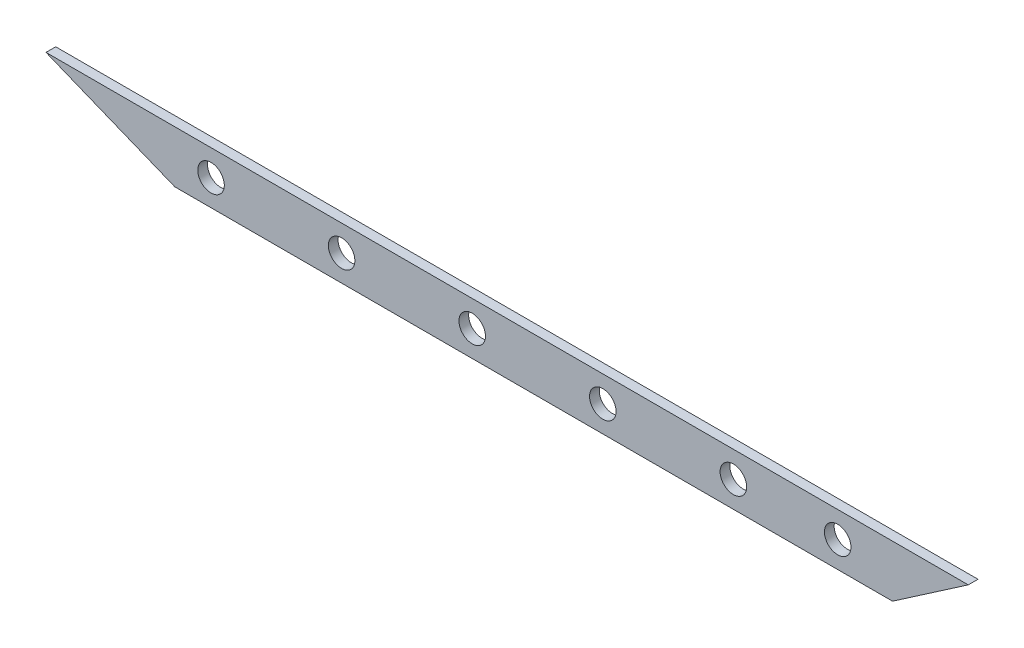
SolidWorks part; units mm, degrees
material "5052-H32"
ref_plane "Front Plane" through (0, 0, 0) normal (0, 0, 1) x (1, 0, 0)
ref_plane "Top Plane" through (0, 0, 0) normal (0, 1, 0) x (1, 0, 0)
ref_plane "Right Plane" through (0, 0, 0) normal (1, 0, 0) x (0, 0, -1)
sketch "Sketch1" plane through (0, 0, 0) normal (0, 0, 1) x (1, 0, 0)
  line L1 (428.1206, 33.3333) -> (428.1206, 28.5708)
  line L3 (428.1206, 28.5708) -> (0, 28.5708)
  line L4 (0, 28.5708) -> (-98.8794, 3.851)
  line L6 (-98.8794, 3.851) -> (-31.8794, -96.649)
  line L7 (428.1206, 28.5708) -> (403.1206, -71.149)
  line L9 (403.1206, -71.149) -> (366, -96.649)
  line L10 (-31.8794, -96.649) -> (366, -96.649)
  circle A0 centre (32, -83.899) radius 6.5
  circle A1 centre (96, -83.899) radius 6.5
  circle A2 centre (160, -83.899) radius 6.5
  circle A3 centre (224, -83.899) radius 6.5
  circle A4 centre (288, -83.899) radius 6.5
  circle A5 centre (339.1206, -83.899) radius 6.5
  point P0 (-48.8794, -71.149)
  point P2 (-31.8794, -96.649)
  point P8 (48, -83.899)
  point P9 (403.1206, -71.149)
  dimension "D2" = 16
  dimension "D4" = 64
  dimension "D1" = 25.5
  dimension "D3" = 75
  dimension "D5" = 25
  dimension "D6" = 64
  dimension "D7" = 527
  dimension "D9" = 64
  dimension "D10" = 64
  dimension "D11" = 64
  dimension "D12" = 123.69
  dimension "D13" = 12.75
extrude "Boss-Extrude1" add sketch "Sketch1" along normal blind 4.7625 contours L3 L4 L6 L10 L9 L7
extrude "Cut-Extrude1" cut sketch "Sketch1<4>" along normal through all contours A0 | A1 | A2 | A3 | A4 | A5 region at (32, -83.899, 0)
sketch "Sketch1<4>" plane through (0, 0, 0) normal (0, 0, 1) x (1, 0, 0) same geometry as "Sketch1"
sketch "Sketch2" plane through (0, 0, 0) normal (0, 0, -1) x (-1, 0, 0)
  circle A0 centre (-307.1206, -83.899) radius 6.5
  circle A2 centre (-249.5603, -111.8778) radius 6.5
  circle A3 centre (-192, -83.899) radius 6.5
  circle A4 centre (-128, -83.899) radius 6.5
  circle A5 centre (-64, -83.899) radius 6.5
  circle A6 centre (0, -83.899) radius 6.5
  dimension "D2" = 0
  dimension "D3" = 64
  dimension "D4" = 64
  dimension "D5" = 64
  dimension "D6" = 64
  dimension "D7" = 64
  dimension "D1" = 32
sketch "Sketch5" plane through (0, 0, 0) normal (0, 0, -1) x (-1, 0, 0)
  line L0 (48.8794, -71.149) -> (-14.2353, -96.649)
  line L1 (31.8794, -96.649) -> (-366, -96.649) construction
  line L2 (-14.2353, -96.649) -> (31.8794, -96.649)
  line L3 (31.8794, -96.649) -> (48.8794, -71.149)
  line L6 (-366, -96.649) -> (-403.1206, -71.149)
  line L7 (-403.1206, -71.149) -> (-352, -71.149)
  line L9 (-352, -71.149) -> (-326.5, -96.649)
  line L11 (-366, -96.649) -> (-326.5, -96.649)
  dimension "D1" = 22
  dimension "D2" = 45
extrude "Cut-Extrude2" [suppressed] cut sketch "Sketch5" against normal up to next
sketch "Sketch6" plane through (0, 0, 4.7625) normal (0, 0, 1) x (1, 0, 0)
  line L0 (-48.8794, -71.149) -> (14.2353, -96.649)
  line L1 (-31.8794, -96.649) -> (366, -96.649) construction
  line L2 (14.2353, -96.649) -> (-31.8794, -96.649)
  line L3 (-31.8794, -96.649) -> (-48.8794, -71.149)
  dimension "D1" = 158
extrude "Cut-Extrude3" cut sketch "Sketch6" against normal blind 10
sketch "Sketch7" plane through (0, 0, 4.7625) normal (0, 0, 1) x (1, 0, 0)
  line L0 (-48.8794, -71.149) -> (403.1206, -71.149)
  line L1 (-48.8794, -71.149) -> (-98.8794, 3.851)
  line L2 (-98.8794, 3.851) -> (0, 28.5708)
  line L3 (0, 28.5708) -> (428.1206, 28.5708)
  line L4 (428.1206, 28.5708) -> (403.1206, -71.149)
extrude "Cut-Extrude4" cut sketch "Sketch7" against normal up to next
